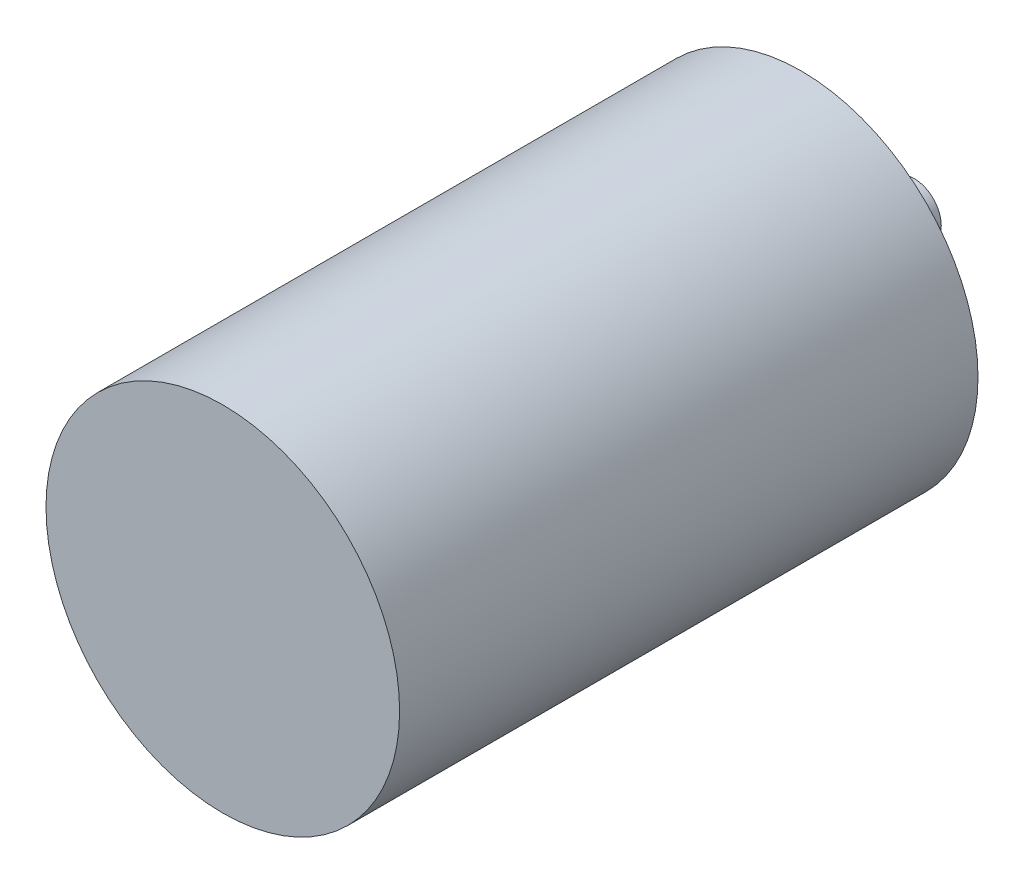
SolidWorks part; units mm, degrees
ref_plane "Plano frontal" through (0, 0, 0) normal (0, 0, 1) x (1, 0, 0)
ref_plane "Plano superior" through (0, 0, 0) normal (0, 1, 0) x (1, 0, 0)
ref_plane "Plano direito" through (0, 0, 0) normal (1, 0, 0) x (0, 0, -1)
sketch "Esboço1" plane through (0, 0, 0) normal (0, 0, 1) x (1, 0, 0)
  circle A0 centre (0, 0) radius 39.125
  circle A1 centre (0, 0) radius 26 construction
  circle A2 centre (0, 0) radius 6
  point P4 (0, 26)
  point P5 (-26, 0)
  point P6 (26, 0)
  point P7 (0, -26)
  dimension "D1" = 78.25
  dimension "D2" = 52
  dimension "D3" = 12
extrude "Ressalto-extrusão1" add sketch "Esboço1" along normal blind 128 contours A0
hole_wizard "Furo roscado de M51" positions "Esboço2" profile "Esboço3" tap size "M5" standard "ISO"
sketch "Esboço2" plane through (0, 0, 0) normal (0, 0, -1) x (-1, 0, 0)
  point P4 (0, 26)
  point P7 (-26, 0)
  point P10 (0, -26)
  point P13 (26, 0)
sketch "Esboço3" plane through (0, 26, 0) normal (1, 0, 0) x (0, 1, 0)
  line L0 (0, 0) -> (0, 11.2618)
  line L1 (0, 11.2618) -> (2.1, 10)
  line L2 (2.1, 10) -> (2.1, 0.425)
  line L3 (2.1, 0.425) -> (2.525, 0)
  line L5 (2.525, 0) -> (0, 0)
  line L6 (-2.1, 0.425) -> (-2.525, 0) construction
  line L10 (0, 11.2618) -> (-2.1, 10) construction
  line L11 (0, -6.35) -> (0, 107.95) construction
  dimension "Tap Drill Dia." = 4.2
  dimension "Tap Drill Depth" = 10
  dimension "Near C'Sink Dia." = 5.05
  dimension "Near C'Sink Angle" = 90
  dimension "Drill Angle" = 118
cosmetic thread "Rosca de furo1"
cosmetic thread "Rosca de furo2"
cosmetic thread "Rosca de furo3"
cosmetic thread "Rosca de furo4"
extrude "Ressalto-extrusão2" add sketch "Esboço1<4>" against normal blind 25 contours A2
sketch "Esboço1<4>" plane through (0, 0, 0) normal (0, 0, 1) x (1, 0, 0) same geometry as "Esboço1"
